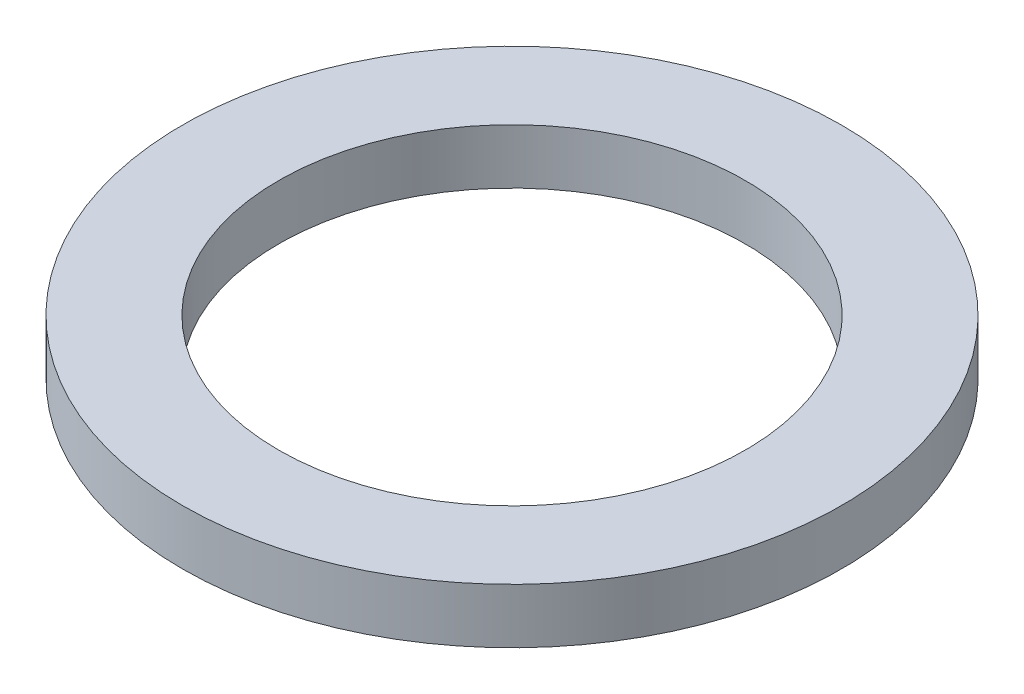
SolidWorks part; units mm, degrees
ref_plane "Front Plane" through (0, 0, 0) normal (0, 0, 1) x (1, 0, 0)
ref_plane "Top Plane" through (0, 0, 0) normal (0, 1, 0) x (1, 0, 0)
ref_plane "Right Plane" through (0, 0, 0) normal (1, 0, 0) x (0, 0, -1)
sketch "Sketch1" plane through (0, 0, 0) normal (0, 1, 0) x (1, 0, 0)
  circle A0 centre (0, 0) radius 60
  dimension "FLANGE_OD" = 120
extrude "Boss-Extrude1" add sketch "Sketch1" along normal blind 10
sketch "Sketch2" plane through (0, 0, 0) normal (0, 1, 0) x (1, 0, 0)
  circle A0 centre (0, 0) radius 42.5
  dimension "BORE_D" = 85
extrude "Cut-Extrude1" cut sketch "Sketch2" along normal through all
sketch "Sketch3" plane through (0, 10, 0) normal (0, 1, 0) x (1, 0, 0)
  circle A0 centre (0, 0) radius 23.802 construction
  circle A1 centre (-23.802, 0) radius 2.6827
  dimension "BOLT_D" = 5.3654
  dimension "BOLT_PCD" = 47.604
extrude "Cut-Extrude2" cut sketch "Sketch3" against normal blind 6.5918 rebuild error yes
pattern_circular "CirPattern1" count 3 over 360 rebuild error yes
